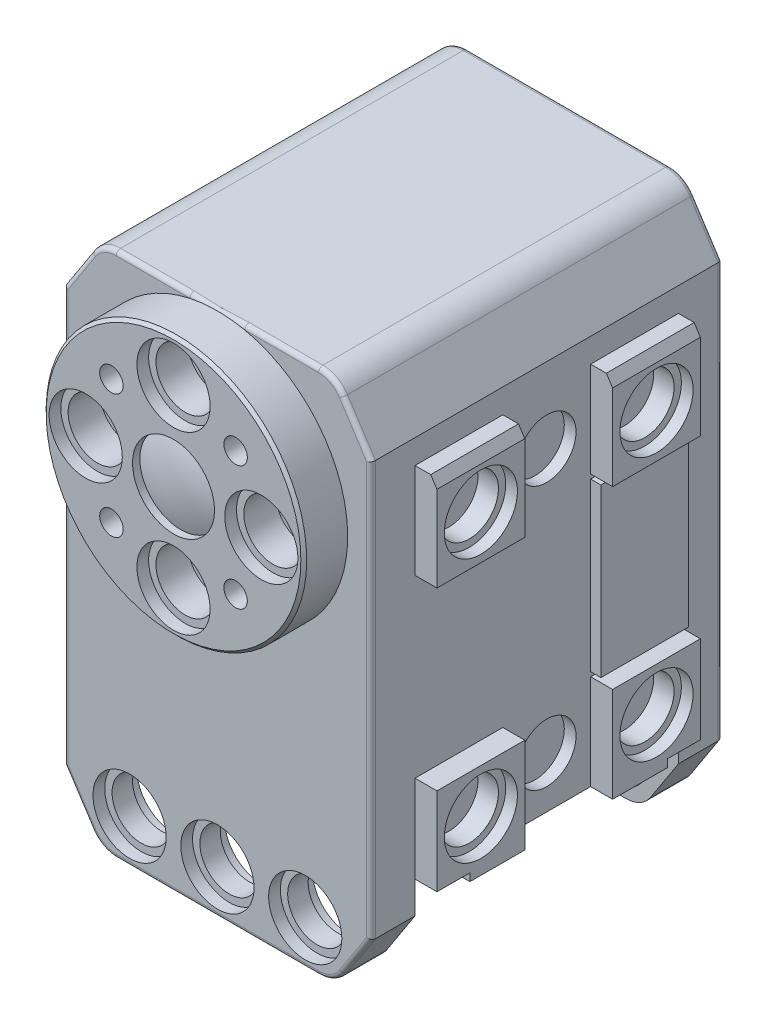
SolidWorks part; units mm, degrees
ref_plane "Front Plane" through (0, 0, 0) normal (0, 0, 1) x (1, 0, 0)
ref_plane "Top Plane" through (0, 0, 0) normal (0, 1, 0) x (1, 0, 0)
ref_plane "Right Plane" through (0, 0, 0) normal (1, 0, 0) x (0, 0, -1)
ref_plane "Plane1" through (0, 0, 0) normal (0, -1, 0) x (1, 0, 0)
sketch "Sketch1" plane through (0, 0, 0) normal (0, -1, 0) x (1, 0, 0)
  line L0 (0, 15) -> (0, 12)
  line L1 (0, 12) -> (8.9, 12)
  line L2 (8.9, 12) -> (8.9, 15)
  line L3 (8.9, 15) -> (2.8, 15)
  line L4 (2.8, 15) -> (2.8, 14.5)
  line L5 (0, 15.0001) -> (0, 12) construction
  arc A0 (2.8, 14.5) -> (0, 15) centre (0, 6.91) ccw
revolve "Revolve1" add sketch "Sketch1" angle 360 about L5 other way angle 360 reverse direction yes
ref_plane "Plane2" through (0, 0, 12) normal (0, 0, 1) x (1, 0, 0)
sketch "Sketch2" plane through (0, 0, 12) normal (0, 0, 1) x (1, 0, 0)
  line L0 (10.5, -23.1503) -> (10.5, 5.1503)
  line L1 (10.5, 5.1503) -> (8, 9)
  line L2 (8, 9) -> (-8, 9)
  line L3 (-8, 9) -> (-10.5, 5.1503)
  line L4 (-10.5, 5.1503) -> (-10.5, -23.1503)
  line L5 (-10.5, -23.1503) -> (-8, -27)
  line L6 (-8, -27) -> (8, -27)
  line L7 (8, -27) -> (10.5, -23.1503)
extrude "Boss-Extrude1" add sketch "Sketch2" against normal blind 18.75
sketch "Sketch3" plane through (0, 0, -6.75) normal (0, 0, -1) x (-1, 0, 0)
  line L0 (-6, -21.5) -> (-10.5, -21.5)
  line L1 (-10.5, -21.5) -> (-10.5, -23.1503)
  line L2 (-10.5, -23.1503) -> (-8, -27)
  line L3 (-8, -27) -> (8, -27)
  line L4 (8, -27) -> (10.5, -23.1503)
  line L5 (10.5, -23.1503) -> (10.5, -21.5)
  line L6 (10.5, -21.5) -> (6, -21.5)
  line L7 (4, -22.5) -> (-4, -22.5)
  arc A0 (6, -21.5) -> (4, -22.5) centre (6, -24) ccw
  arc A1 (-4, -22.5) -> (-6, -21.5) centre (-6, -24) ccw
extrude "Cut-Extrude1" cut sketch "Sketch3" against normal blind 13.5
sketch "Sketch4" plane through (0, 0, 6.75) normal (0, 0, -1) x (-1, 0, 0)
  line L0 (-6, -20.975) -> (-10.5, -20.975)
  line L1 (-10.5, -20.975) -> (-10.5, -23.1503)
  line L2 (-10.5, -23.1503) -> (-8, -27)
  line L3 (-8, -27) -> (8, -27)
  line L4 (8, -27) -> (10.5, -23.1503)
  line L5 (10.5, -23.1503) -> (10.5, -20.975)
  line L6 (10.5, -20.975) -> (6, -20.975)
  line L7 (3.3731, -22.5) -> (-3.3731, -22.5)
  arc A0 (-3.3731, -22.5) -> (-6, -20.975) centre (-6, -24) ccw
  arc A1 (6, -20.975) -> (3.3731, -22.5) centre (6, -24) ccw
extrude "Cut-Extrude2" cut sketch "Sketch4" against normal blind 2.25
sketch "Sketch5" plane through (10.5, 0, 0) normal (1, 0, 0) x (0, 0, -1)
  line L0 (6.75, 5.1503) -> (6.75, -21.5)
  line L1 (6.75, -21.5) -> (3, -21.5)
  line L2 (3, -21.5) -> (3, 5.1503)
  line L3 (3, 5.1503) -> (6.75, 5.1503)
extrude "Boss-Extrude2" add sketch "Sketch5" along normal blind 1.5
sketch "Sketch6" plane through (10.5, 0, 0) normal (1, 0, 0) x (0, 0, -1)
  line L0 (-9, -20.975) -> (-9, -15)
  line L1 (-9, -15) -> (-3, -15)
  line L2 (-3, -15) -> (-3, -21.5)
  line L3 (-3, -21.5) -> (-6.75, -21.5)
  line L4 (-6.75, -21.5) -> (-6.75, -20.975)
  line L5 (-6.75, -20.975) -> (-9, -20.975)
extrude "Boss-Extrude3" add sketch "Sketch6" along normal blind 1.5
sketch "Sketch7" plane through (-10.5, 0, 0) normal (-1, 0, 0) x (0, 0, 1)
  line L0 (9, -15) -> (9, -20.975)
  line L1 (9, -20.975) -> (6.75, -20.975)
  line L2 (6.75, -20.975) -> (6.75, -21.5)
  line L3 (6.75, -21.5) -> (3, -21.5)
  line L4 (3, -21.5) -> (3, -15)
  line L5 (3, -15) -> (9, -15)
extrude "Boss-Extrude4" add sketch "Sketch7" along normal blind 1.5
sketch "Sketch8" plane through (-10.5, 0, 0) normal (-1, 0, 0) x (0, 0, 1)
  line L0 (-3, 5.1503) -> (-3, -21.5)
  line L1 (-3, -21.5) -> (-6.75, -21.5)
  line L2 (-6.75, -21.5) -> (-6.75, 5.1503)
  line L3 (-6.75, 5.1503) -> (-3, 5.1503)
extrude "Boss-Extrude5" add sketch "Sketch8" along normal blind 1.5
sketch "Sketch9" plane through (0, 5.1503, 0) normal (0, 1, 0) x (-1, 0, 0)
  line L0 (-12, -3) -> (-12, -6.75)
  line L1 (-12, -6.75) -> (-10.5, -6.75)
  line L2 (-10.5, -6.75) -> (-10.5, -3)
  line L3 (-10.5, -3) -> (-12, -3)
extrude "Cut-Extrude3" cut sketch "Sketch9" against normal blind 20.1503
sketch "Sketch10" plane through (0, 5.1503, 0) normal (0, 1, 0) x (-1, 0, 0)
  line L0 (10.5, -3) -> (10.5, -6.75)
  line L1 (10.5, -6.75) -> (12, -6.75)
  line L2 (12, -6.75) -> (12, -3)
  line L3 (12, -3) -> (10.5, -3)
extrude "Cut-Extrude4" cut sketch "Sketch10" against normal blind 20.1503
sketch "Sketch11" plane through (0, 0, -6.75) normal (0, 0, -1) x (-1, 0, 0)
  line L0 (12, -20.975) -> (6, -20.975)
  line L1 (3.3731, -22.5) -> (-3.3731, -22.5)
  line L2 (-6, -20.975) -> (-12, -20.975)
  line L3 (-12, -20.975) -> (-12, -15)
  line L4 (-12, -15) -> (-10.5, -15)
  line L5 (-10.5, -15) -> (-10.5, 5.1503)
  line L6 (-10.5, 5.1503) -> (-8, 9)
  line L7 (-8, 9) -> (8, 9)
  line L8 (8, 9) -> (10.5, 5.1503)
  line L9 (10.5, 5.1503) -> (10.5, -15)
  line L10 (10.5, -15) -> (12, -15)
  line L11 (12, -15) -> (12, -20.975)
  arc A0 (6, -20.975) -> (3.3731, -22.5) centre (6, -24) ccw
  arc A1 (-3.3731, -22.5) -> (-6, -20.975) centre (-6, -24) ccw
extrude "Boss-Extrude6" add sketch "Sketch11" along normal blind 2.25
sketch "Sketch12" plane through (0, 0, -9) normal (0, 0, -1) x (-1, 0, 0)
  line L0 (-8, 9) -> (8, 9)
  line L1 (8, 9) -> (10.5, 5.1503)
  line L2 (10.5, 5.1503) -> (10.5, -23.1503)
  line L3 (10.5, -23.1503) -> (8, -27)
  line L4 (8, -27) -> (-8, -27)
  line L5 (-8, -27) -> (-10.5, -23.1503)
  line L6 (-10.5, -23.1503) -> (-10.5, 5.1503)
  line L7 (-10.5, 5.1503) -> (-8, 9)
extrude "Boss-Extrude7" add sketch "Sketch12" along normal blind 3
sketch "Sketch13" plane through (0, 0, -9) normal (0, 0, 1) x (1, 0, 0)
  circle A0 centre (-6, -24) radius 2.5
extrude "Cut-Extrude5" cut sketch "Sketch13" against normal blind 0.8
sketch "Sketch14" plane through (0, 0, -12) normal (0, 0, -1) x (-1, 0, 0)
  circle A0 centre (6, -24) radius 2.5
extrude "Cut-Extrude6" cut sketch "Sketch14" against normal blind 0.8
sketch "Sketch15" plane through (0, 0, -11.2) normal (0, 0, -1) x (-1, 0, 0)
  circle A0 centre (6, -24) radius 2
extrude "Cut-Extrude7" cut sketch "Sketch15" against normal up to next
hole_wizard "M4x0.7 Tapped Hole1" positions "Sketch17" profile "Sketch16" tap size "M4x0.7" standard "ANSI Metric"
sketch "Sketch17" plane through (0, 0, -9) normal (0, 0, 1) x (1, 0, 0)
  point P0 (0, -24)
sketch "Sketch16" plane through (0, -24, -9) normal (1, 0, 0) x (0, -1, 0)
  line L0 (0, 0) -> (0, 2.2)
  line L1 (0, 2.2) -> (2.5, 2.2)
  line L2 (2.5, 2.2) -> (2.5, 1.4)
  line L3 (2.5, 1.4) -> (2, 1.4)
  line L4 (2, 1.4) -> (2, 0)
  line L5 (2, 0) -> (0, 0)
  line L10 (0, 2.2) -> (-2.5, 2.2) construction
  line L11 (0, -6.35) -> (0, 107.95) construction
  dimension "Tap Drill Dia." = 5
  dimension "Tap Drill Depth" = 2.2
  dimension "Thread Major Dia." = 4
  dimension "Thread Depth" = 1.4
  dimension "Drill Angle" = 180
sketch "Sketch18" plane through (0, 0, -9) normal (0, 0, 1) x (1, 0, 0)
  circle A0 centre (6, -24) radius 2.5
extrude "Cut-Extrude8" cut sketch "Sketch18" against normal blind 0.8
sketch "Sketch19" plane through (0, 0, -12) normal (0, 0, -1) x (-1, 0, 0)
  circle A0 centre (-6, -24) radius 2.5
extrude "Cut-Extrude9" cut sketch "Sketch19" against normal blind 0.8
sketch "Sketch20" plane through (0, 0, -11.2) normal (0, 0, -1) x (-1, 0, 0)
  circle A0 centre (-6, -24) radius 2
extrude "Cut-Extrude10" cut sketch "Sketch20" against normal up to next
sketch "Sketch21" plane through (10.5, 0, 0) normal (1, 0, 0) x (0, 0, -1)
  line L0 (9, -3) -> (3, -3)
  line L1 (3, -3) -> (3, 3.5)
  line L2 (3, 3.5) -> (9, 3.5)
  line L3 (9, 3.5) -> (9, -3)
extrude "Boss-Extrude8" add sketch "Sketch21" along normal blind 1.5
sketch "Sketch22" plane through (10.5, 0, 0) normal (1, 0, 0) x (0, 0, -1)
  line L0 (-9, 3.5) -> (-3, 3.5)
  line L1 (-3, 3.5) -> (-3, -3)
  line L2 (-3, -3) -> (-9, -3)
  line L3 (-9, -3) -> (-9, 3.5)
extrude "Boss-Extrude9" add sketch "Sketch22" along normal blind 1.5
sketch "Sketch23" plane through (10.5, 0, 0) normal (1, 0, 0) x (0, 0, -1)
  line L0 (9, -14.7) -> (3, -14.7)
  line L1 (3, -14.7) -> (3, -3.3)
  line L2 (3, -3.3) -> (9, -3.3)
  line L3 (9, -3.3) -> (9, -14.7)
extrude "Boss-Extrude10" add sketch "Sketch23" along normal blind 0.7
sketch "Sketch24" plane through (-10.5, 0, 0) normal (-1, 0, 0) x (0, 0, 1)
  line L0 (-9, 3.5) -> (-3, 3.5)
  line L1 (-3, 3.5) -> (-3, -3)
  line L2 (-3, -3) -> (-9, -3)
  line L3 (-9, -3) -> (-9, 3.5)
extrude "Boss-Extrude11" add sketch "Sketch24" along normal blind 1.5
sketch "Sketch25" plane through (-10.5, 0, 0) normal (-1, 0, 0) x (0, 0, 1)
  line L0 (9, -3) -> (3, -3)
  line L1 (3, -3) -> (3, 3.5)
  line L2 (3, 3.5) -> (9, 3.5)
  line L3 (9, 3.5) -> (9, -3)
extrude "Boss-Extrude12" add sketch "Sketch25" along normal blind 1.5
sketch "Sketch26" plane through (-10.5, 0, 0) normal (-1, 0, 0) x (0, 0, 1)
  line L0 (-9, -3.3) -> (-3, -3.3)
  line L1 (-3, -3.3) -> (-3, -14.7)
  line L2 (-3, -14.7) -> (-9, -14.7)
  line L3 (-9, -14.7) -> (-9, -3.3)
extrude "Boss-Extrude13" add sketch "Sketch26" along normal blind 0.7
ref_plane "Plane3" through (0, -24, 0) normal (0, 1, 0) x (1, 0, 0)
sketch "Sketch27" plane through (0, -24, 0) normal (0, 1, 0) x (1, 0, 0)
  line L0 (8.5, -9) -> (6, -9)
  line L1 (6, -9) -> (6, -12)
  line L2 (6, -12) -> (8.5, -12)
  line L3 (8.5, -12) -> (8.5, -11.2)
  line L4 (8.5, -11.2) -> (8, -11.2)
  line L5 (8, -11.2) -> (8, -9.8)
  line L6 (8, -9.8) -> (8.5, -9.8)
  line L7 (8.5, -9.8) -> (8.5, -9)
  line L8 (6, -9) -> (6, -12) construction
revolve "Cut-Revolve1" cut sketch "Sketch27" angle 360 about L8 reverse direction yes
sketch "Sketch28" plane through (0, -24, 0) normal (0, 1, 0) x (1, 0, 0)
  line L0 (-3.5, -9) -> (-6, -9)
  line L1 (-6, -9) -> (-6, -12)
  line L2 (-6, -12) -> (-3.5, -12)
  line L3 (-3.5, -12) -> (-3.5, -11.2)
  line L4 (-3.5, -11.2) -> (-4, -11.2)
  line L5 (-4, -11.2) -> (-4, -9.8)
  line L6 (-4, -9.8) -> (-3.5, -9.8)
  line L7 (-3.5, -9.8) -> (-3.5, -9)
  line L8 (-6, -9) -> (-6, -12) construction
revolve "Cut-Revolve2" cut sketch "Sketch28" angle 360 about L8 reverse direction yes
sketch "Sketch29" plane through (0, -24, 0) normal (0, 1, 0) x (1, 0, 0)
  line L0 (2.5, -9) -> (0, -9)
  line L1 (0, -9) -> (0, -12)
  line L2 (0, -12) -> (2.5, -12)
  line L3 (2.5, -12) -> (2.5, -11.2)
  line L4 (2.5, -11.2) -> (2, -11.2)
  line L5 (2, -11.2) -> (2, -9.8)
  line L6 (2, -9.8) -> (2.5, -9.8)
  line L7 (2.5, -9.8) -> (2.5, -9)
  line L8 (0, -9) -> (0, -12) construction
revolve "Cut-Revolve3" cut sketch "Sketch29" angle 360 about L8 reverse direction yes
hole_wizard "CBORE for M3.5 Hex Head Machine Screw1" positions "Sketch31" profile "Sketch30" counterbore size "M3.5" standard "ANSI Metric"
sketch "Sketch31" plane through (0, 0, -12) normal (0, 0, -1) x (-1, 0, 0)
  point P0 (6, 0)
  point P1 (0, 0)
  point P2 (-6, 0)
sketch "Sketch30" plane through (-6, 0, -12) normal (1, 0, 0) x (0, 1, 0)
  line L0 (0, 0) -> (0, 3)
  line L1 (0, 3) -> (2, 3)
  line L2 (2, 3) -> (2, 0.8)
  line L3 (2, 0.8) -> (2.5, 0.8)
  line L4 (2.5, 0.8) -> (2.5, 0)
  line L5 (2.5, 0) -> (0, 0)
  line L10 (0, 3) -> (-2, 3) construction
  line L11 (0, -6.35) -> (0, 107.95) construction
  dimension "Hole Dia." = 4
  dimension "Hole Depth" = 3
  dimension "C'Bore Dia." = 5
  dimension "C'Bore Depth" = 0.8
  dimension "Drill Angle" = 180
hole_wizard "Ø4.0 (4) Diameter Hole1" positions "Sketch33" profile "Sketch32" hole size "Ø4.0" standard "ANSI Metric"
sketch "Sketch33" plane through (-10.5, 0, 0) normal (-1, 0, 0) x (0, 0, 1)
  point P0 (0, 0)
  point P1 (0, -18)
sketch "Sketch32" plane through (-10.5, 0, 0) normal (0, 1, 0) x (0, 0, 1)
  line L0 (0, 0) -> (0, 0.8)
  line L1 (0, 0.8) -> (2, 0.8)
  line L2 (2, 0.8) -> (2, 0)
  line L5 (2, 0) -> (0, 0)
  line L10 (0, 0.8) -> (-2, 0.8) construction
  line L11 (0, -6.35) -> (0, 107.95) construction
  dimension "Hole Dia." = 4
  dimension "Hole Depth" = 0.8
  dimension "Drill Angle" = 180
hole_wizard "Ø4.0 (4) Diameter Hole2" positions "Sketch35" profile "Sketch34" hole size "Ø4.0" standard "ANSI Metric"
sketch "Sketch35" plane through (10.5, 0, 0) normal (1, 0, 0) x (0, 0, -1)
  point P0 (0, 0)
  point P1 (0, -18)
sketch "Sketch34" plane through (10.5, 0, 0) normal (0, 1, 0) x (0, 0, -1)
  line L0 (0, 0) -> (0, 0.8)
  line L1 (0, 0.8) -> (2, 0.8)
  line L2 (2, 0.8) -> (2, 0)
  line L5 (2, 0) -> (0, 0)
  line L10 (0, 0.8) -> (-2, 0.8) construction
  line L11 (0, -6.35) -> (0, 107.95) construction
  dimension "Hole Dia." = 4
  dimension "Hole Depth" = 0.8
  dimension "Drill Angle" = 180
hole_wizard "CBORE for M3.5 Hex Head Machine Screw2" positions "Sketch37" profile "Sketch36" counterbore size "M3.5" standard "ANSI Metric"
sketch "Sketch37" plane through (-12, 0, 0) normal (-1, 0, 0) x (0, 0, 1)
  point P0 (6, -18)
  point P1 (-6, -18)
  point P2 (-6, 0)
  point P3 (6, 0)
sketch "Sketch36" plane through (-12, -18, 6) normal (0, 1, 0) x (0, 0, 1)
  line L0 (0, 0) -> (0, 2.2)
  line L1 (0, 2.2) -> (2, 2.2)
  line L2 (2, 2.2) -> (2, 0.8)
  line L3 (2, 0.8) -> (2.5, 0.8)
  line L4 (2.5, 0.8) -> (2.5, 0)
  line L5 (2.5, 0) -> (0, 0)
  line L10 (0, 2.2) -> (-2, 2.2) construction
  line L11 (0, -6.35) -> (0, 107.95) construction
  dimension "Hole Dia." = 4
  dimension "Hole Depth" = 2.2
  dimension "C'Bore Dia." = 5
  dimension "C'Bore Depth" = 0.8
  dimension "Drill Angle" = 180
hole_wizard "Ø1.6 (1.6) Diameter Hole1" positions "Sketch39" profile "Sketch38" hole size "Ø1.6" standard "ANSI Metric"
sketch "Sketch39" plane through (0, 0, 15) normal (0, 0, 1) x (1, 0, 0)
  point P0 (4.2426, 4.2426)
  point P1 (-4.2426, 4.2426)
  point P2 (4.2426, -4.2426)
  point P3 (-4.2426, -4.2426)
sketch "Sketch38" plane through (4.2426, 4.2426, 15) normal (1, 0, 0) x (0, -1, 0)
  line L0 (0, 0) -> (0, 3)
  line L1 (0, 3) -> (0.8, 3)
  line L2 (0.8, 3) -> (0.8, 0)
  line L5 (0.8, 0) -> (0, 0)
  line L10 (0, 3) -> (-0.8, 3) construction
  line L11 (0, -6.35) -> (0, 107.95) construction
  dimension "Hole Dia." = 1.6
  dimension "Hole Depth" = 3
  dimension "Drill Angle" = 180
hole_wizard "CBORE for M3.5 Hex Head Machine Screw3" positions "Sketch41" profile "Sketch40" counterbore size "M3.5" standard "ANSI Metric"
sketch "Sketch41" plane through (12, 0, 0) normal (1, 0, 0) x (0, 0, -1)
  point P0 (6, -18)
  point P1 (-6, -18)
  point P2 (6, 0)
  point P3 (-6, 0)
sketch "Sketch40" plane through (12, -18, -6) normal (0, 1, 0) x (0, 0, -1)
  line L0 (0, 0) -> (0, 2.2)
  line L1 (0, 2.2) -> (2, 2.2)
  line L2 (2, 2.2) -> (2, 0.8)
  line L3 (2, 0.8) -> (2.5, 0.8)
  line L4 (2.5, 0.8) -> (2.5, 0)
  line L5 (2.5, 0) -> (0, 0)
  line L10 (0, 2.2) -> (-2, 2.2) construction
  line L11 (0, -6.35) -> (0, 107.95) construction
  dimension "Hole Dia." = 4
  dimension "Hole Depth" = 2.2
  dimension "C'Bore Dia." = 5
  dimension "C'Bore Depth" = 0.8
  dimension "Drill Angle" = 180
hole_wizard "CBORE for M3.5 Hex Head Machine Screw4" positions "Sketch43" profile "Sketch42" counterbore size "M3.5" standard "ANSI Metric"
sketch "Sketch43" plane through (0, 0, 15) normal (0, 0, 1) x (1, 0, 0)
  point P0 (6, 0)
  point P1 (0, 6)
  point P2 (-6, 0)
  point P3 (0, -6)
sketch "Sketch42" plane through (6, 0, 15) normal (1, 0, 0) x (0, -1, 0)
  line L0 (0, 0) -> (0, 3)
  line L1 (0, 3) -> (2, 3)
  line L2 (2, 3) -> (2, 0.8)
  line L3 (2, 0.8) -> (2.5, 0.8)
  line L4 (2.5, 0.8) -> (2.5, 0)
  line L5 (2.5, 0) -> (0, 0)
  line L10 (0, 3) -> (-2, 3) construction
  line L11 (0, -6.35) -> (0, 107.95) construction
  dimension "Hole Dia." = 4
  dimension "Hole Depth" = 3
  dimension "C'Bore Dia." = 5
  dimension "C'Bore Depth" = 0.8
  dimension "Drill Angle" = 180
fillet "Fillet1" radius 2 6 edges at (8, -27, -10.5) (8, -27, 10.5) (8, 9, 0) (-8, 9, 0) (-8, -27, -10.5) (-8, -27, 10.5) tangent propagation no
chamfer "Chamfer1" distance 0.6595 angle 33 4 edges at (12, 3.5, -6) (12, 3.5, 6) (-12, 3.5, -6) (-12, 3.5, 6) first distance on face at (12, 0, -8.5) first distance on face at (12, 0, 3.5) first distance on face at (-12, 0, -3.5) first distance on face at (-12, 0, 8.5)
chamfer "Chamfer4" distance 0.2 angle 45 1 edges at (-8.9, 0, 15)
fillet "Fillet2" radius 0.3 24 edges at (-9.5457, -24.6198, 12) (-7.8684, -26.7576, 12) (0, -27, 12) (7.8684, -26.7576, 12) (9.5457, -24.6198, 12) (10.5, -9, 12) (-10.5, -9, 12) (9.5457, 6.6198, 12) (7.8684, 8.7576, 12) (0, 9, 12) (-7.8684, 8.7576, 12) (-9.5457, 6.6198, 12) (9.5457, -24.6198, -12) (-9.5457, -24.6198, -12) (7.8684, -26.7576, -12) (-7.8684, -26.7576, -12) (0, -27, -12) (-10.5, -9, -12) (10.5, -9, -12) (-9.5457, 6.6198, -12) (9.5457, 6.6198, -12) (-7.8684, 8.7576, -12) (7.8684, 8.7576, -12) (0, 9, -12)
ref_plane "Plane4" through (0, 9, 0) normal (0, 1, 0) x (1, 0, 0)
sketch "Sketch58" plane through (0, 0, 15) normal (0, 0, 1) x (1, 0, 0)
  circle A0 centre (0, 0) radius 8.7
extrude "Boss-Extrude26" add sketch "Sketch58" along normal blind 45 separate body contours A0
sketch "Sketch60" plane through (0, 0, 15) normal (0, 0, -1) x (-1, 0, 0)
  circle A1 centre (-6, 0) radius 2
  circle A3 centre (0, -6) radius 2
  circle A4 centre (6, 0) radius 2
  circle A5 centre (0, 6) radius 2
extrude "Cut-Extrude17" cut sketch "Sketch60" against normal blind 7
sketch "Sketch61" plane through (0, 0, 60) normal (0, 0, 1) x (1, 0, 0)
  line L1 (-3.7873, -8.6983) -> (4.1327, -8.6983)
  line L2 (-3.7873, -8.6983) -> (-3.7873, -4.6983)
  line L3 (-3.7873, -4.6983) -> (4.1327, -4.6983)
  line L4 (4.1327, -8.6983) -> (4.1327, -4.6983)
  circle A1 centre (0, 0) radius 8.7 construction
  point P4 (0.1727, -8.6983)
  dimension "D1" = 7.92
  dimension "D2" = 4
extrude "Boss-Extrude27" add sketch "Sketch61" against normal blind 10 separate body contours L3 L4 L1 L2
fillet "Fillet5" radius 0.4 3 edges at (4.1327, -8.6983, 55) (0.1727, -8.6983, 50) (-3.7873, -8.6983, 55)
delete or keep bodies "Body-Delete/Keep 1" type delete bodies bodies 164 163
